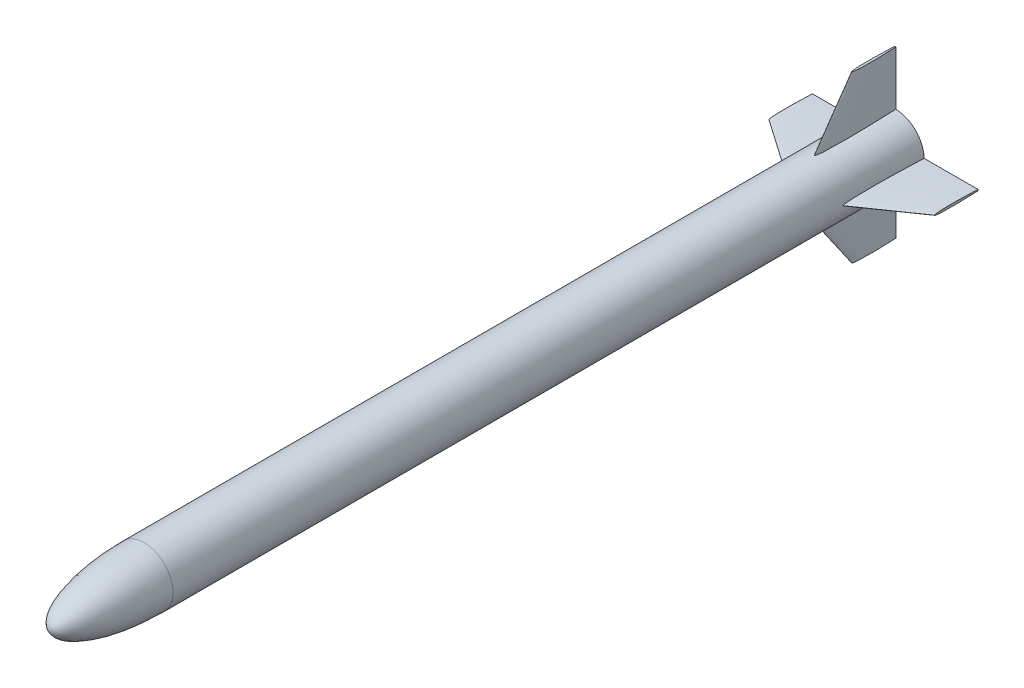
SolidWorks part; units mm, degrees
ref_plane "Front Plane" through (0, 0, 0) normal (0, 0, 1) x (1, 0, 0)
ref_plane "Top Plane" through (0, 0, 0) normal (0, 1, 0) x (1, 0, 0)
ref_plane "Right Plane" through (0, 0, 0) normal (1, 0, 0) x (0, 0, -1)
sketch "Sketch2" plane through (0, 0, 0) normal (1, 0, 0) x (0, 0, -1)
  line L0 (254, 78.3229) -> (2289.4925, 78.3229)
  line L1 (2289.4925, 78.3229) -> (2289.4925, 0)
  line L2 (2289.4925, 0) -> (0, 0)
  line L3 (0, 0) -> (-254, 0) construction
  line L4 (0, 0) -> (2.1037, 78.3229) construction
  ellipse E0 centre (254, 0) end of major axis (0, 0) minor radius 78.3229 (254, 78.3229) -> (0, 0) ccw
  dimension "D1" = 2035.4925
  dimension "D2" = 254
  dimension "D3" = 78.3229
  dimension "D5" = 254
  dimension "D4" = 78.3229
revolve "Revolve1" add sketch "Sketch2" angle 360 about L2
sketch "Sketch3" plane through (0, 0, -2289.4925) normal (0, 0, -1) x (-1, 0, 0)
  circle A0 centre (0, 0) radius 43.942
  dimension "D1" = 87.884
extrude "Boss-Extrude1" add sketch "Sketch3" along normal blind 15.24
ref_plane "Plane1" through (0, 254, 0) normal (0, 1, 0) x (1, 0, 0)
sketch "Sketch4" plane through (0, 254, 0) normal (0, 1, 0) x (1, 0, 0)
  line L1 (-1.5875, 2083.1175) -> (1.5875, 2083.1175)
  line L2 (-1.5875, 2083.1175) -> (-1.5875, 2286.3175)
  line L3 (-1.5875, 2286.3175) -> (1.5875, 2286.3175)
  line L4 (1.5875, 2083.1175) -> (1.5875, 2286.3175)
  line L5 (78.3229, 2289.4925) -> (-78.3229, 2289.4925) construction
  point P6 (0, 2286.3175)
  dimension "D1" = 3.175
  dimension "D2" = 3.175
  dimension "D3" = 203.2
extrude "Boss-Extrude2" add sketch "Sketch4" against normal up to surface (175.6932 mm away) up to face at (-78.3229, 0, -254)
sketch "Sketch5" plane through (-1.5875, 0, 0) normal (-1, 0, 0) x (0, 0, 1)
  line L0 (-2286.3175, 224.3568) -> (-2184.7175, 224.3568)
  line L1 (-2286.3175, 78.3068) -> (-2286.3175, 254) construction
  line L2 (-2184.7175, 224.3568) -> (-2083.1175, 78.3068)
  line L3 (-2083.1175, 78.3068) -> (-2083.1175, 254)
  line L4 (-2083.1175, 254) -> (-2286.3175, 254)
  line L5 (-2286.3175, 254) -> (-2286.3175, 224.3568)
  dimension "D1" = 101.6
  dimension "D2" = 146.05
extrude "Cut-Extrude1" cut sketch "Sketch5" against normal up to next
sketch "Sketch6" plane through (0, 224.3568, 0) normal (0, 1, 0) x (1, 0, 0)
  line L0 (0, 2324.1) -> (0, 2171.7) construction
  spline S0 degree 4 poles (0, 2171.7) (0.051, 2171.7006) (0.1231, 2171.7139) (0.2087, 2171.7542) (0.3062, 2171.8284) (0.3808, 2171.9014) (0.4592, 2171.9956) (0.5527, 2172.1319) (0.6711, 2172.3415) (0.8367, 2172.7057) (1.0914, 2173.434) (1.3865, 2174.6081) (1.6836, 2176.1867) (2.0477, 2178.6899) (2.3957, 2181.9018) (2.8436, 2187.452) (3.2338, 2195.3473) (3.4845, 2204.9737) (3.5657, 2216.3247) (3.4973, 2227.6786) (3.3169, 2239.0263) (3.0506, 2250.3803) (2.7588, 2260.3008) (2.4732, 2268.8226) (2.1645, 2277.3095) (1.8846, 2284.4423) (1.593, 2291.4551) (1.2729, 2298.6554) (1.0213, 2304.1337) (0.7286, 2310.1507) (0.4762, 2315.2186) (0.091, 2322.4894) (-0.1374, 2326.6114) (-0.4882, 2332.7319) (-0.6703, 2335.6828) (-0.8182, 2338.1424) (-0.8568, 2338.7185) (-0.8967, 2339.3772) knots 0 0 0 0 0 0.001189 0.001745 0.002211 0.002902 0.003665 0.004655 0.006135 0.008619 0.013162 0.022972 0.034881 0.04679 0.073274 0.099757 0.167217 0.234678 0.302138 0.369599 0.437059 0.504519 0.57198 0.60571 0.63944 0.7069 0.74063 0.774361 0.808091 0.841821 0.875551 0.909281 0.954641 0.97732 0.98866 1 1 1 1 1 construction
  spline S1 degree 4 poles (0, 2171.7) (0.051, 2171.7006) (0.1231, 2171.7139) (0.2087, 2171.7542) (0.3062, 2171.8284) (0.3808, 2171.9014) (0.4592, 2171.9956) (0.5527, 2172.1319) (0.6711, 2172.3415) (0.8367, 2172.7057) (1.0914, 2173.434) (1.3865, 2174.6081) (1.6836, 2176.1867) (2.0477, 2178.6899) (2.3957, 2181.9018) (2.8436, 2187.452) (3.2338, 2195.3473) (3.4845, 2204.9737) (3.5657, 2216.3247) (3.4973, 2227.6786) (3.3169, 2239.0263) (3.0506, 2250.3803) (2.7588, 2260.3008) (2.4732, 2268.8226) (2.1645, 2277.3095) (1.8846, 2284.4423) (1.593, 2291.4551) (1.2729, 2298.6554) (1.0213, 2304.1337) (0.7286, 2310.1507) (0.4762, 2315.2186) (0.2102, 2320.239) (0.0709, 2322.8117) (0, 2324.1) knots 0 0 0 0 0 0.001189 0.001745 0.002211 0.002902 0.003665 0.004655 0.006135 0.008619 0.013162 0.022972 0.034881 0.04679 0.073274 0.099757 0.167217 0.234678 0.302138 0.369599 0.437059 0.504519 0.57198 0.60571 0.63944 0.7069 0.74063 0.774361 0.808091 0.841821 0.875551 0.909281 0.909281 0.909281 0.909281 0.909281
  spline S2 degree 4 poles (0, 2171.7) (-0.051, 2171.7006) (-0.1231, 2171.7139) (-0.2087, 2171.7542) (-0.3062, 2171.8284) (-0.3808, 2171.9014) (-0.4592, 2171.9956) (-0.5527, 2172.1319) (-0.6711, 2172.3415) (-0.8367, 2172.7057) (-1.0914, 2173.434) (-1.3865, 2174.6081) (-1.6836, 2176.1867) (-2.0477, 2178.6899) (-2.3957, 2181.9018) (-2.8436, 2187.452) (-3.2338, 2195.3473) (-3.4845, 2204.9737) (-3.5657, 2216.3247) (-3.4973, 2227.6786) (-3.3169, 2239.0263) (-3.0506, 2250.3803) (-2.7588, 2260.3008) (-2.4732, 2268.8226) (-2.1645, 2277.3095) (-1.8846, 2284.4423) (-1.593, 2291.4551) (-1.2729, 2298.6554) (-1.0213, 2304.1337) (-0.7286, 2310.1507) (-0.4762, 2315.2186) (-0.2102, 2320.239) (-0.0709, 2322.8117) (0, 2324.1) knots 0 0 0 0 0 0.001189 0.001745 0.002211 0.002902 0.003665 0.004655 0.006135 0.008619 0.013162 0.022972 0.034881 0.04679 0.073274 0.099757 0.167217 0.234678 0.302138 0.369599 0.437059 0.504519 0.57198 0.60571 0.63944 0.7069 0.74063 0.774361 0.808091 0.841821 0.875551 0.909281 0.909281 0.909281 0.909281 0.909281
ref_plane "Plane2" through (0, 78.232, 0) normal (0, 1, 0) x (1, 0, 0)
sketch "Sketch7" plane through (0, 78.232, 0) normal (0, 1, 0) x (1, 0, 0)
  line L0 (0, 2324.1) -> (0, 2070.1) construction
  spline S0 degree 4 poles (0, 2070.1) (0.0342, 2070.1002) (0.1014, 2070.1073) (0.2316, 2070.1502) (0.3603, 2070.247) (0.4625, 2070.3536) (0.562, 2070.481) (0.6446, 2070.6032) (0.7505, 2070.7852) (0.8922, 2071.0745) (1.0839, 2071.5498) (1.3694, 2072.4381) (1.8161, 2074.2937) (2.2988, 2077.1802) (2.77, 2080.9905) (3.2968, 2086.605) (3.7697, 2093.44) (4.2835, 2103.6731) (4.696, 2117.3079) (4.925, 2133.2199) (4.9497, 2151.4074) (4.8018, 2169.593) (4.557, 2185.5057) (4.283, 2199.1414) (3.9649, 2212.7806) (3.6673, 2224.1378) (3.3402, 2235.5096) (2.9883, 2246.8566) (2.6904, 2255.9678) (2.3035, 2267.2859) (1.805, 2280.9991) (1.282, 2294.483) (0.7524, 2307.184) (0.3684, 2315.9782) (0.0635, 2322.737) (-0.1342, 2327.0197) (-0.4722, 2334.1824) (-0.736, 2339.5059) (-1.0136, 2345.0628) (-1.1551, 2347.7422) (-1.2484, 2349.5509) knots 0 0 0 0 0 0.000483 0.000965 0.00193 0.00226 0.00259 0.00327 0.004035 0.005264 0.007185 0.010582 0.017344 0.032491 0.048939 0.065387 0.097843 0.130299 0.19521 0.260121 0.325033 0.389944 0.454856 0.487311 0.519767 0.584679 0.617134 0.64959 0.682046 0.714502 0.779413 0.844324 0.87678 0.893008 0.909236 0.931927 0.954618 0.977309 1 1 1 1 1 construction
  spline S1 degree 4 poles (0, 2070.1) (0.0342, 2070.1002) (0.1014, 2070.1073) (0.2316, 2070.1502) (0.3603, 2070.247) (0.4625, 2070.3536) (0.562, 2070.481) (0.6446, 2070.6032) (0.7505, 2070.7852) (0.8922, 2071.0745) (1.0839, 2071.5498) (1.3694, 2072.4381) (1.8161, 2074.2937) (2.2988, 2077.1802) (2.77, 2080.9905) (3.2968, 2086.605) (3.7697, 2093.44) (4.2835, 2103.6731) (4.696, 2117.3079) (4.925, 2133.2199) (4.9497, 2151.4074) (4.8018, 2169.593) (4.557, 2185.5057) (4.283, 2199.1414) (3.9649, 2212.7806) (3.6673, 2224.1378) (3.3402, 2235.5096) (2.9883, 2246.8566) (2.6904, 2255.9678) (2.3035, 2267.2859) (1.805, 2280.9991) (1.282, 2294.483) (0.7524, 2307.184) (0.3684, 2315.9782) (0.1425, 2320.9863) (0.0475, 2323.0676) (0, 2324.1) knots 0 0 0 0 0 0.000483 0.000965 0.00193 0.00226 0.00259 0.00327 0.004035 0.005264 0.007185 0.010582 0.017344 0.032491 0.048939 0.065387 0.097843 0.130299 0.19521 0.260121 0.325033 0.389944 0.454856 0.487311 0.519767 0.584679 0.617134 0.64959 0.682046 0.714502 0.779413 0.844324 0.87678 0.893008 0.909236 0.909236 0.909236 0.909236 0.909236
  spline S2 degree 4 poles (0, 2070.1) (-0.0342, 2070.1002) (-0.1014, 2070.1073) (-0.2316, 2070.1502) (-0.3603, 2070.247) (-0.4625, 2070.3536) (-0.562, 2070.481) (-0.6446, 2070.6032) (-0.7505, 2070.7852) (-0.8922, 2071.0745) (-1.0839, 2071.5498) (-1.3694, 2072.4381) (-1.8161, 2074.2937) (-2.2988, 2077.1802) (-2.77, 2080.9905) (-3.2968, 2086.605) (-3.7697, 2093.44) (-4.2835, 2103.6731) (-4.696, 2117.3079) (-4.925, 2133.2199) (-4.9497, 2151.4074) (-4.8018, 2169.593) (-4.557, 2185.5057) (-4.283, 2199.1414) (-3.9649, 2212.7806) (-3.6673, 2224.1378) (-3.3402, 2235.5096) (-2.9883, 2246.8566) (-2.6904, 2255.9678) (-2.3035, 2267.2859) (-1.805, 2280.9991) (-1.282, 2294.483) (-0.7524, 2307.184) (-0.3684, 2315.9782) (-0.1425, 2320.9863) (-0.0475, 2323.0676) (0, 2324.1) knots 0 0 0 0 0 0.000483 0.000965 0.00193 0.00226 0.00259 0.00327 0.004035 0.005264 0.007185 0.010582 0.017344 0.032491 0.048939 0.065387 0.097843 0.130299 0.19521 0.260121 0.325033 0.389944 0.454856 0.487311 0.519767 0.584679 0.617134 0.64959 0.682046 0.714502 0.779413 0.844324 0.87678 0.893008 0.909236 0.909236 0.909236 0.909236 0.909236
  point P0 (0, 0)
loft "Loft12" add profiles "Sketch6", "Sketch7" connector at (0, 224.3568, -2171.7) connector at (0, 78.232, -2070.1)
sketch "Sketch8" plane through (0, 78.232, 0) normal (0, -1, 0) x (1, 0, 0)
  line L0 (-1.4702, -2289.4925) -> (1.4702, -2289.4925) construction
  line L1 (-4.9625, -2289.4925) -> (2.5426, -2289.4925)
  line L2 (-4.9625, -2289.4925) -> (-4.9625, -2339.479)
  line L3 (-4.9625, -2339.479) -> (2.5426, -2339.479)
  line L4 (2.5426, -2289.4925) -> (2.5426, -2339.479)
  point P5 (-4.9625, -2292.2072)
extrude "Cut-Extrude3" cut sketch "Sketch8" against normal through all
pattern_circular "CirPattern1" count 4 over 360 about axis through (0, 0, -2289.4925) along (0, 0, -1) of "Boss-Extrude2", "Cut-Extrude1", "Loft12", "Cut-Extrude3"
equation "\"Body Tube Length\"= 80.1375"
equation "\"D1@Sketch2\"=\"Body Tube Length\""
equation "\"Retainer Diameter\"= 3.46"
equation "\"D1@Sketch3\"=\"Retainer Diameter\""
equation "\"Retainer Height\"= 0.6"
equation "\"D1@Boss-Extrude1\"=\"Retainer Height\""
equation "\"Fin Offset\"= .125"
equation "\"D1@Sketch4\"=\"Fin Offset\""
equation "\"Fin Thickness\"= .125"
equation "\"D2@Sketch4\"=\"Fin Thickness\""
equation "\"Fin Root Chord\"= 8"
equation "\"D3@Sketch4\"=\"Fin Root Chord\""
equation "\"Fin Tip Chord\"= 4"
equation "\"D1@Sketch5\"=\"Fin Tip Chord\""
equation "\"Fin Height\"= 5.75"
equation "\"D2@Sketch5\"=\"Fin Height\""
equation "\"Fin Epoxy Fillet Radius\"=0.1"
equation "\"Nosecone Length\"= 10"
equation "\"D2@Sketch2\"=\"Nosecone Length\""
equation "\"Rocket Radius\"=3.08358"
equation "\"D3@Sketch2\"= \"Rocket Radius\""
equation "\"D5@Sketch2\"=\"Nosecone Length\""
equation "\"D4@Sketch2\"=\"Rocket Radius\""
